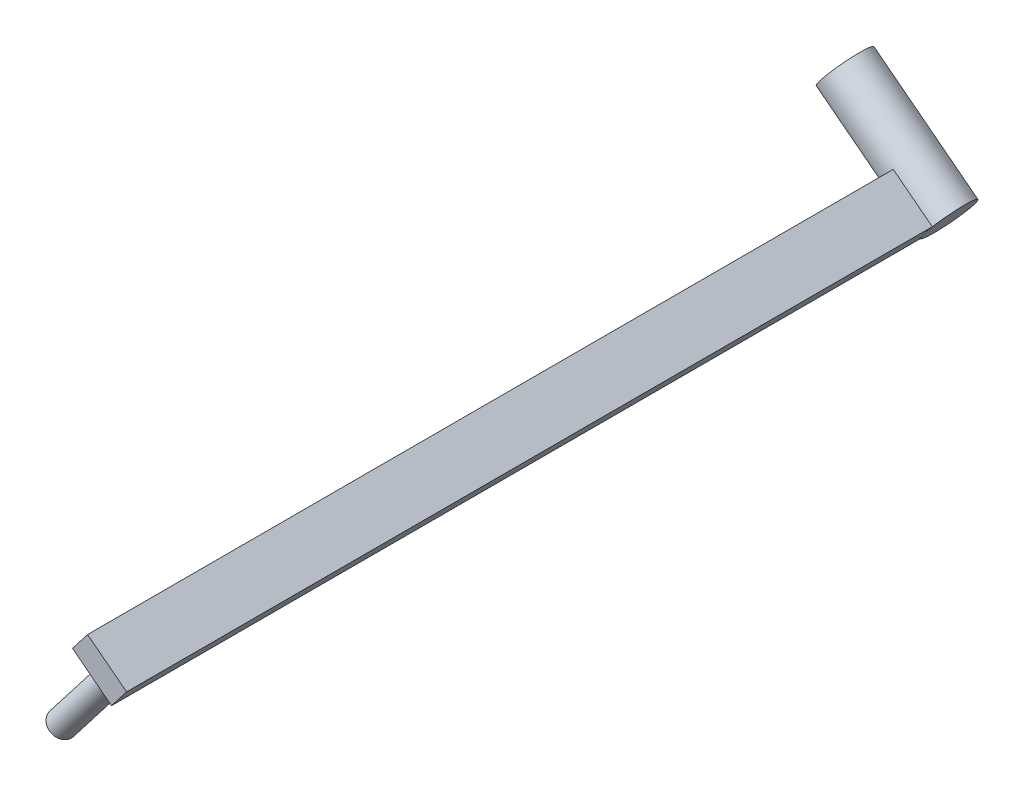
SolidWorks part; units mm, degrees
ref_plane "Front Plane" through (0, 0, 0) normal (0, 0, 1) x (1, 0, 0)
ref_plane "Top Plane" through (0, 0, 0) normal (0, 1, 0) x (1, 0, 0)
ref_plane "Right Plane" through (0, 0, 0) normal (1, 0, 0) x (0, 0, -1)
sketch "Sketch1" plane through (-196.8423, 152.1371, 0) normal (0.7912, -0.6115, 0) x (0, 0, -1)
  line L0 (151.99, 21.1) -> (144.49, 21.1) construction
  line L1 (196.1229, 22.6) -> (147.1229, 22.6)
  line L3 (196.3139, 21.1) -> (147.1229, 21.1)
  line L4 (147.1229, 22.6) -> (147.1229, 21.1)
  circle A0 centre (197.5129, 22.0013) radius 1.5
  circle A1 centre (197.5129, 22.0013) radius 1.5135 construction
  line M15 (194.0125, 31.6983) -> (194.0136, 6.0011)
  circle M20 centre (197.5129, 22.0013) radius 1.5135
  dimension "D2" = 3
  dimension "D1" = 1.5
  dimension "D3" = 49
extrude "Boss-Extrude1" add sketch "Sketch1" against normal blind 5 contours A0 region at (-183.388, 169.545, -197.5129)
extrude "Boss-Extrude2" add sketch "Sketch1<3>" along normal blind 3 contours A0 | L1 L4 L3 M15 | L3 L1 M20 M15 region at (-183.4866, 169.4174, -195.0442) region at (-183.388, 169.545, -197.5129) region at (-183.4805, 169.4253, -170.5679)
sketch "Sketch1<3>" plane through (-196.8423, 152.1371, 0) normal (0.7912, -0.6115, 0) x (0, 0, -1) same geometry as "Sketch1"
sketch "Sketch2" plane through (12.9032, 16.6948, 0) normal (-0.6115, -0.7912, 0) x (0.7912, -0.6115, 0)
  circle A0 centre (-246.825, -147.9775) radius 0.75
extrude "Boss-Extrude3" add sketch "Sketch2" along normal blind 5
